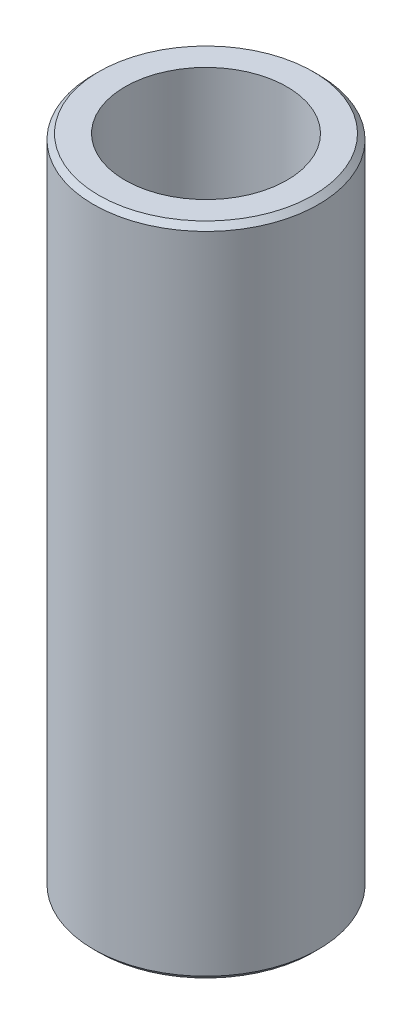
SolidWorks part; units mm, degrees
ref_plane "Front Plane" through (0, 0, 0) normal (0, 0, 1) x (1, 0, 0)
ref_plane "Top Plane" through (0, 0, 0) normal (0, 1, 0) x (1, 0, 0)
ref_plane "Right Plane" through (0, 0, 0) normal (1, 0, 0) x (0, 0, -1)
sketch "Sketch1" plane through (0, 0, 0) normal (0, 1, 0) x (1, 0, 0)
  circle A0 centre (0, 0) radius 60
  dimension "SHAFT_OD" = 120
extrude "Boss-Extrude1" add sketch "Sketch1" along normal blind 349.7534
sketch "Sketch2" plane through (0, 0, 0) normal (0, 1, 0) x (1, 0, 0)
  circle A0 centre (0, 0) radius 43.1967
  dimension "BORE_D" = 86.3934
extrude "Cut-Extrude1" cut sketch "Sketch2" along normal through all
chamfer "Chamfer1" distance 2.8366 angle 45 2 edges at (0, 349.7534, 60) (0, 0, 60)
